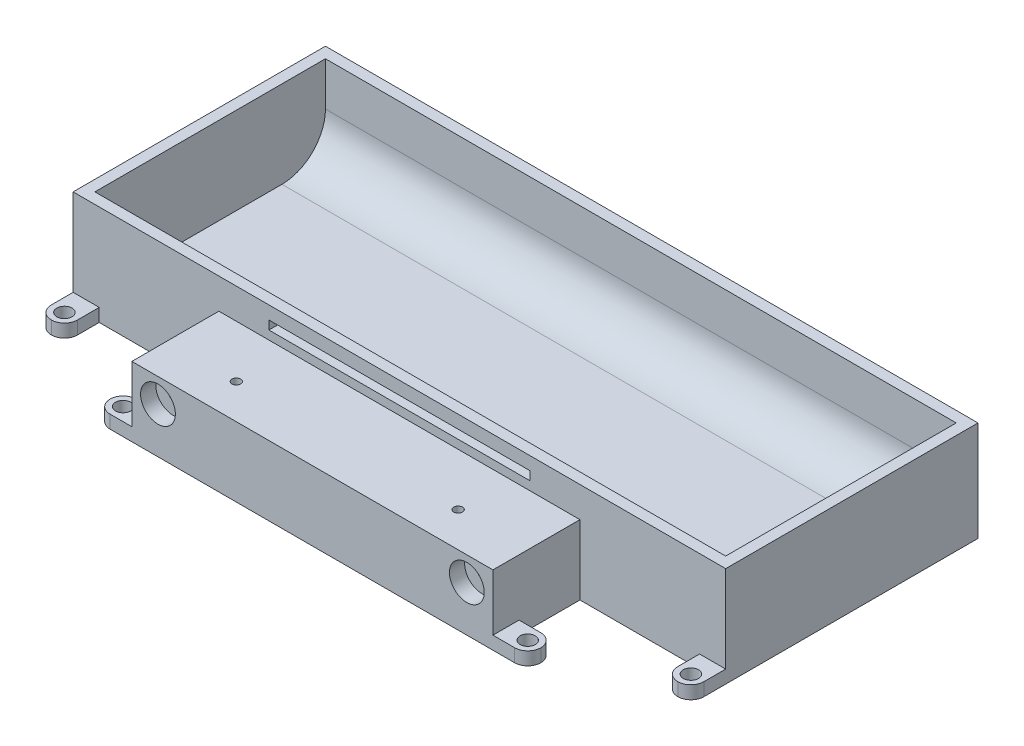
SolidWorks part; units mm, degrees
ref_plane "정면" through (0, 0, 0) normal (0, 0, 1) x (1, 0, 0)
ref_plane "윗면" through (0, 0, 0) normal (0, 1, 0) x (1, 0, 0)
ref_plane "우측면" through (0, 0, 0) normal (1, 0, 0) x (0, 0, -1)
sketch "스케치1" plane through (0, 0, 0) normal (0, 1, 0) x (1, 0, 0)
  line L1 (-41.5, 10) -> (41.5, 10)
  line L2 (-41.5, 10) -> (-41.5, -10)
  line L3 (-41.5, -10) -> (41.5, -10)
  line L4 (41.5, 10) -> (41.5, -10)
  line L5 (-41.5, 10) -> (41.5, -10) construction
  line L6 (-41.5, -10) -> (41.5, 10) construction
  point P0 (0, 0)
  dimension "D1" = 83
  dimension "D2" = 20
extrude "보스-돌출1" add sketch "스케치1" along normal blind 16
sketch "스케치2" plane through (0, 0, 10) normal (0, 0, 1) x (1, 0, 0)
  line L3 (-41.5, 16) -> (41.5, 16) construction
  line L4 (-41.5, 16) -> (-41.5, 0) construction
  line L6 (41.5, 16) -> (41.5, 0) construction
  circle A2 centre (-35.5, 10.5) radius 4
  circle A3 centre (35.5, 10.5) radius 4
  dimension "D1" = 8
  dimension "D2" = 8
  dimension "D4" = 5.5
  dimension "D5" = 6
  dimension "D6" = 6
extrude "컷-돌출1" cut sketch "스케치2" against normal blind 3.5
sketch "스케치3" plane through (0, 16, 0) normal (0, 1, 0) x (1, 0, 0)
  line L0 (-41.5, 10) -> (-41.5, -10) construction
  line L1 (-41.5, -10) -> (41.5, -10) construction
  line L2 (41.5, -10) -> (41.5, 10) construction
  circle A0 centre (-25.5, -2) radius 1
  circle A1 centre (25.5, -2) radius 1
  dimension "D1" = 2
  dimension "D2" = 16
  dimension "D3" = 8
  dimension "D4" = 16
  dimension "D5" = 8
extrude "컷-돌출2" cut sketch "스케치3" against normal blind 10
sketch "스케치6" plane through (0, 0, 6.5) normal (0, 0, 1) x (1, 0, 0)
  circle A0 centre (-35.5, 10.5) radius 1
  circle A1 centre (35.5, 10.5) radius 1
  dimension "D1" = 2
extrude "컷-돌출5" cut sketch "스케치6" against normal blind 8
sketch "스케치7" plane through (0, 0, -10) normal (0, 0, -1) x (-1, 0, 0)
  line L0 (0, 0) -> (0, 16) construction
  line L1 (-41.5, 16) -> (41.5, 16) construction
  line L2 (-41.5, 0) -> (41.5, 0) construction
  line L3 (-75, 3) -> (75, 3)
  line L4 (-75, 3) -> (-75, 0)
  line L5 (-75, 0) -> (75, 0)
  line L6 (75, 3) -> (75, 0)
  line L7 (-75, 3) -> (75, 0) construction
  line L8 (-75, 0) -> (75, 3) construction
  point P5 (0, 1.5)
  dimension "D1" = 150
  dimension "D2" = 3
extrude "보스-돌출2" add sketch "스케치7" along normal blind 58
sketch "스케치8" plane through (0, 3, 0) normal (0, 1, 0) x (1, 0, 0)
  line L0 (-72.5, 65.5) -> (-72.5, 12.5)
  line L1 (-75, 68) -> (75, 68)
  line L2 (-75, 68) -> (-75, 10)
  line L3 (-75, 10) -> (75, 10)
  line L4 (75, 68) -> (75, 10)
  line L5 (-72.5, 12.5) -> (72.5, 12.5)
  line L6 (72.5, 65.5) -> (72.5, 12.5)
  line L7 (-72.5, 65.5) -> (72.5, 65.5)
  dimension "D1" = 2.5
extrude "보스-돌출3" add sketch "스케치8" along normal blind 20
fillet "필렛1" radius 10 2 edges at (0, 3, -12.5) (0, 3, -65.5)
sketch "스케치9" plane through (-75, 0, 0) normal (-1, 0, 0) x (0, 0, 1)
  line L0 (-68, 0) -> (-68, 23) construction
  line L1 (-68, 18) -> (-66, 18)
  line L2 (-68, 18) -> (-68, 20)
  line L3 (-68, 20) -> (-66, 20)
  line L4 (-66, 18) -> (-66, 20)
  line L5 (-10, 0) -> (-10, 23) construction
  line L6 (-10, 18) -> (-12, 18)
  line L7 (-10, 18) -> (-10, 20)
  line L8 (-10, 20) -> (-12, 20)
  line L9 (-12, 18) -> (-12, 20)
  line L10 (-68, 23) -> (-10, 23) construction
  dimension "D1" = 2
  dimension "D2" = 2
  dimension "D3" = 2
  dimension "D4" = 2
  dimension "D5" = 3
  dimension "D6" = 3
extrude "컷-돌출6" cut sketch "스케치9" against normal blind 60 from offset 45 offset against normal yes
sketch "스케치10" plane through (0, 0, -10) normal (0, 0, 1) x (1, 0, 0)
  line L1 (-75, 0) -> (-69, 0)
  line L2 (-75, 0) -> (-75, 3)
  line L3 (-75, 3) -> (-69, 3)
  line L4 (-69, 0) -> (-69, 3)
  line L5 (75, 0) -> (69, 0)
  line L6 (75, 0) -> (75, 3)
  line L7 (75, 3) -> (69, 3)
  line L8 (69, 0) -> (69, 3)
  dimension "D1" = 6
  dimension "D2" = 3
extrude "보스-돌출4" add sketch "스케치10" along normal blind 8
sketch "스케치11" plane through (0, 0, -68) normal (0, 0, -1) x (-1, 0, 0)
  line L0 (-75, 0) -> (75, 0) construction
  line L1 (-36, 0) -> (-30, 0)
  line L2 (-36, 0) -> (-36, 3)
  line L3 (-36, 3) -> (-30, 3)
  line L4 (-30, 0) -> (-30, 3)
  line L6 (30, 0) -> (36, 0)
  line L7 (30, 0) -> (30, 3)
  line L8 (30, 3) -> (36, 3)
  line L9 (36, 0) -> (36, 3)
  dimension "D1" = 6
  dimension "D2" = 3
  dimension "D3" = 60
  dimension "D4" = 30
extrude "보스-돌출5" add sketch "스케치11" along normal blind 8
sketch "스케치12" plane through (-41.5, 0, 0) normal (-1, 0, 0) x (0, 0, 1)
  line L6 (10, 0) -> (4, 0)
  line L7 (10, 0) -> (10, 3)
  line L8 (10, 3) -> (4, 3)
  line L9 (4, 0) -> (4, 3)
  dimension "D1" = 6
  dimension "D2" = 3
extrude "보스-돌출6" add sketch "스케치12" along normal blind 8
sketch "스케치13" plane through (41.5, 0, 0) normal (1, 0, 0) x (0, 0, -1)
  line L1 (-10, 0) -> (-4, 0)
  line L2 (-10, 0) -> (-10, 3)
  line L3 (-10, 3) -> (-4, 3)
  line L4 (-4, 0) -> (-4, 3)
  dimension "D1" = 6
  dimension "D2" = 3
extrude "보스-돌출7" add sketch "스케치13" along normal blind 8
fillet "필렛2" radius 3 12 edges at (69, 1.5, -2) (75, 1.5, -2) (-75, 1.5, -2) (-69, 1.5, -2) (-36, 1.5, -76) (-30, 1.5, -76) (30, 1.5, -76) (36, 1.5, -76) (-49.5, 1.5, 4) (-49.5, 1.5, 10) (49.5, 1.5, 10) (49.5, 1.5, 4)
sketch "스케치14" plane through (0, 3, 0) normal (0, 1, 0) x (1, 0, 0)
  circle A0 centre (-33, 73) radius 1.75
  circle A1 centre (33, 73) radius 1.75
  circle A2 centre (-46.5, -7) radius 1.75
  circle A3 centre (46.5, -7) radius 1.75
  circle A4 centre (72, 5) radius 1.75
  circle A5 centre (-72, 5) radius 1.75
  dimension "D1" = 3.5
extrude "컷-돌출7" cut sketch "스케치14" against normal through all
